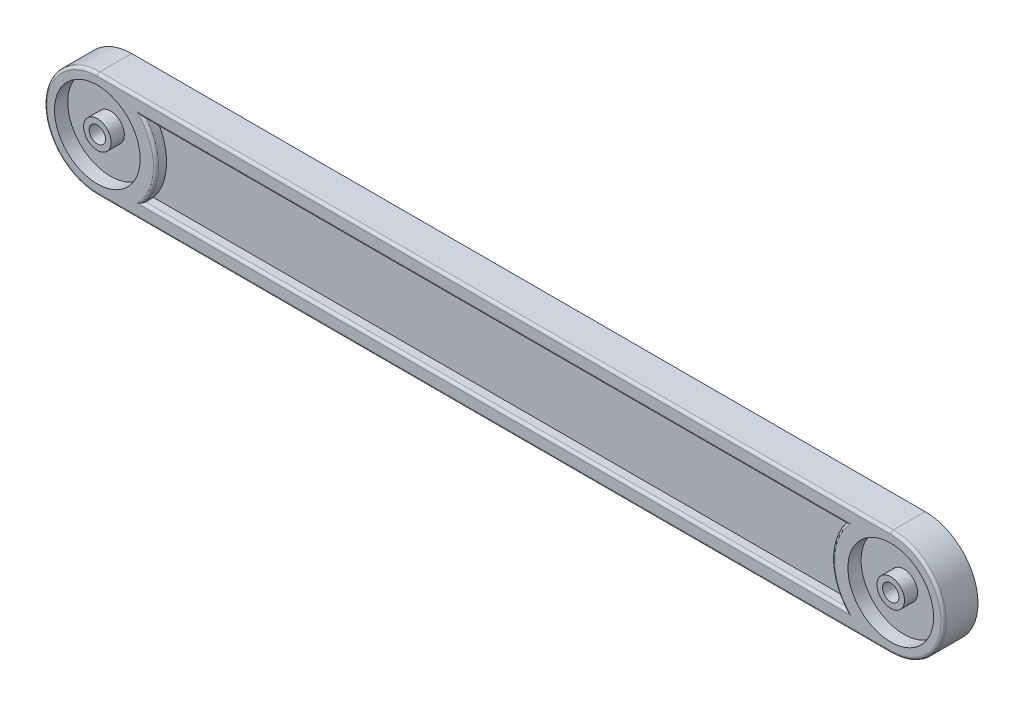
SolidWorks part; units mm, degrees
ref_plane "Front Plane" through (0, 0, 0) normal (0, 0, 1) x (1, 0, 0)
ref_plane "Top Plane" through (0, 0, 0) normal (0, 1, 0) x (1, 0, 0)
ref_plane "Right Plane" through (0, 0, 0) normal (1, 0, 0) x (0, 0, -1)
sketch "Base" plane through (0, 0, 0) normal (0, 0, 1) x (1, 0, 0)
  line L0 (0, 0) -> (0, 4.9397) construction
  line L1 (0, 0) -> (6.6038, 0) construction
  line L2 (-75, 10) -> (75, 10)
  line L3 (-75, -10) -> (75, -10)
  line L4 (-75, 10) -> (-75, -10) construction
  line L5 (75, 10) -> (75, -10) construction
  arc A0 (-75, 10) -> (-75, -10) centre (-75, 0) ccw
  arc A1 (75, 10) -> (75, -10) centre (75, 0) cw
  circle A2 centre (-75, 0) radius 2.6
  circle A3 centre (75, 0) radius 2.6
  circle A4 centre (-75, 0) radius 1.55
  circle A5 centre (75, 0) radius 1.55
  circle A6 centre (75, 0) radius 8.1
  circle A7 centre (-75, 0) radius 8.1
  point P4 (-75, 0)
  point P8 (75, 0)
  dimension "D3" = 5.2
  dimension "D4" = 3.1
  dimension "D5" = 16.2
  dimension "D1" = 20
  dimension "D2" = 150
extrude "Boss-Extrude1" add sketch "Base" along normal blind 4 contours A1 L2 A0 L3 A3 A2 | A2 A4 | A3 A5 | A6 A3 | A7 A2 region at (0, 0, 0) region at (-77.5265, 0, 0) region at (72.4735, 0, 0) region at (67.1291, 0, 0) region at (-82.8709, 0, 0)
extrude "Boss-Extrude2" add sketch "Base<3>" along normal blind 2.5 from surface contours A2 A4 | A3 A5 | A1 L2 A0 L3 A7 A6 region at (0, 0, 0) region at (-77.5265, 0, 0) region at (72.4735, 0, 0) starting at face at (-73.45, 0, 4)
sketch "Base<3>" plane through (0, 0, 0) normal (0, 0, 1) x (1, 0, 0) same geometry as "Base"
sketch "Sketch2" plane through (0, 0, 0) normal (0, 0, -1) x (-1, 0, 0)
  line L1 (72.125, 1.6599) -> (72.125, -1.6599)
  line L2 (72.125, -1.6599) -> (75, -3.3198)
  line L3 (75, -3.3198) -> (77.875, -1.6599)
  line L4 (77.875, -1.6599) -> (77.875, 1.6599)
  line L5 (77.875, 1.6599) -> (75, 3.3198)
  line L6 (75, 3.3198) -> (72.125, 1.6599)
  circle A0 centre (75, 0) radius 2.875 construction
  circle A1 centre (-75, 0) radius 3
  dimension "D2" = 6
  dimension "D1" = 5.75
extrude "Cut-Extrude1" cut sketch "Sketch2" against normal blind 3
sketch "Sketch3" plane through (0, 0, 6.5) normal (0, 0, 1) x (1, 0, 0)
  line L0 (0, 0) -> (0, 18.9172) construction
  line L1 (21.0708, 0) -> (-21.0708, 0) construction
  line L2 (66.3855, -7) -> (-66.3855, -7)
  line L3 (66.3855, 7) -> (-66.3855, 7)
  line L4 (75, -10) -> (-75, -10) construction
  arc A0 (66.3855, -7) -> (66.3855, 7) centre (75, 0) cw
  arc A1 (-66.3855, -7) -> (-66.3855, 7) centre (-75, 0) ccw
  circle A2 centre (75, 0) radius 8.1 construction
  point P8 (0, 0)
  point P11 (0, 0)
  dimension "D2" = 3
  dimension "D1" = 3
extrude "Cut-Extrude2" cut sketch "Sketch3" against normal blind 2
fillet "Fillet1" radius 0.5 8 edges at (0, 7, 6.5) (-63.9, 0, 6.5) (0, -7, 6.5) (63.9, 0, 6.5) (-85, 0, 6.5) (0, 10, 6.5) (85, 0, 6.5) (0, -10, 6.5)
equation "\"Arm_Length\"=150"
equation "\"D2@Base\" = \"Arm_Length\""
